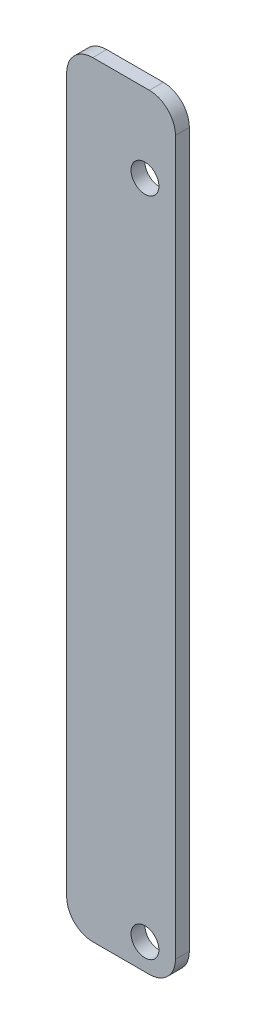
SolidWorks part; units mm, degrees
ref_plane "Front Plane" through (0, 0, 0) normal (0, 0, 1) x (1, 0, 0)
ref_plane "Top Plane" through (0, 0, 0) normal (0, 1, 0) x (1, 0, 0)
ref_plane "Right Plane" through (0, 0, 0) normal (1, 0, 0) x (0, 0, -1)
sketch "Sketch2" plane through (0, 0, 0) normal (0, 0, 1) x (1, 0, 0)
  line L1 (-46.8525, 38.0188) -> (-59.3525, 38.0188)
  line L2 (-46.8525, 38.0188) -> (-46.8525, -49.9812)
  line L3 (-46.8525, -49.9812) -> (-59.3525, -49.9812)
  line L4 (-59.3525, 38.0188) -> (-59.3525, -49.9812)
  point P6 (-59.3525, -49.9812)
  point P9 (-59.3525, 38.0188)
  dimension "D1" = 12.5
  dimension "D2" = 88
extrude "Boss-Extrude1" add sketch "Sketch2" along normal blind 1.6
hole_wizard "Ø3.2 (3.2) Diameter Hole1" positions "Sketch4" profile "Sketch3" hole size "Ø3.2" standard "Ansi Metric"
sketch "Sketch4" plane through (0, 0, 1.6) normal (0, 0, 1) x (1, 0, 0)
  line L0 (-59.3525, -49.9812) -> (-46.8525, -49.9812) construction
  line L1 (-59.3525, 38.0188) -> (-59.3525, -49.9812) construction
  line L2 (-46.8525, 38.0188) -> (-59.3525, 38.0188) construction
  point P0 (-50.3525, 29.0188)
  point P1 (-50.3525, -46.9812)
  dimension "D1" = 3
  dimension "D2" = 9
  dimension "D3" = 9
  dimension "D4" = 9
sketch "Sketch3" plane through (-50.3525, 29.0188, 1.6) normal (1, 0, 0) x (0, -1, 0)
  line L0 (0, 0) -> (0, 2.5614)
  line L1 (0, 2.5614) -> (1.6, 1.6)
  line L2 (1.6, 1.6) -> (1.6, 0)
  line L5 (1.6, 0) -> (0, 0)
  line L10 (0, 2.5614) -> (-1.6, 1.6) construction
  line L11 (0, -6.35) -> (0, 107.95) construction
  dimension "Hole Dia." = 3.2
  dimension "Hole Depth" = 1.6
  dimension "Drill Angle" = 118
fillet "Fillet1" radius 3 4 edges at (-46.8525, 38.0188, 0.8) (-59.3525, 38.0188, 0.8) (-46.8525, -49.9812, 0.8) (-59.3525, -49.9812, 0.8)
